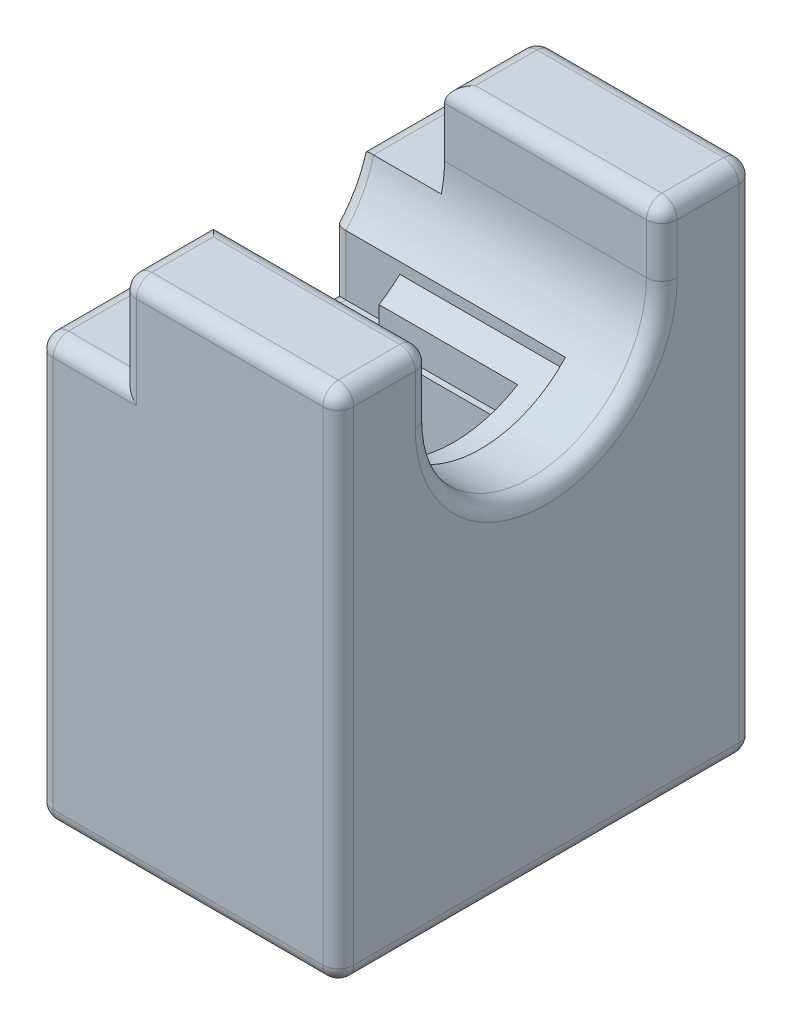
SolidWorks part; units mm, degrees
ref_plane "Front Plane" through (0, 0, 0) normal (0, 0, 1) x (1, 0, 0)
ref_plane "Top Plane" through (0, 0, 0) normal (0, 1, 0) x (1, 0, 0)
ref_plane "Right Plane" through (0, 0, 0) normal (1, 0, 0) x (0, 0, -1)
sketch "Croquis18" plane through (0, 0, 0) normal (0, 1, 0) x (1, 0, 0)
  line L0 (58.8531, -17.2077) -> (58.8531, 10.7923) construction
  line L1 (68.8531, -30.2077) -> (29.8531, -30.2077)
  line L2 (68.8531, -30.2077) -> (68.8531, 23.7923)
  line L3 (68.8531, 23.7923) -> (29.8531, 23.7923)
  line L4 (29.8531, -30.2077) -> (29.8531, 23.7923)
  line L5 (68.8531, -30.2077) -> (29.8531, 23.7923) construction
  line L6 (68.8531, 23.7923) -> (29.8531, -30.2077) construction
  line L7 (40.6531, 17.7923) -> (39.8531, 17.7923) construction
  line L8 (39.8531, 17.7923) -> (39.8531, 14.2923) construction
  line L11 (39.8531, -24.2077) -> (40.6531, -24.2077) construction
  point P0 (0, 0)
  dimension "D1" = 10
  dimension "D2" = 6
  dimension "D3" = 10
  dimension "D4" = 6
extrude "Saliente-Extruir8" add sketch "Croquis18" along normal offset from surface (40.2807 mm away) 1
sketch "Croquis19" plane through (0, 40.2807, 0) normal (0, 1, 0) x (1, 0, 0)
  line L4 (29.8531, -30.2077) -> (68.8531, -30.2077)
  line L5 (68.8531, -30.2077) -> (68.8531, 23.7923)
  line L6 (68.8531, 23.7923) -> (29.8531, 23.7923)
  line L7 (29.8531, 23.7923) -> (29.8531, -30.2077)
  line L8 (29.8531, -30.2077) -> (68.8531, -30.2077)
  line L9 (68.8531, -30.2077) -> (68.8531, 23.7923)
  line L10 (68.8531, 23.7923) -> (29.8531, 23.7923)
  line L11 (29.8531, 23.7923) -> (29.8531, -30.2077)
  dimension "D1" = 0
sketch "Croquis20" plane through (0, 40.2807, 0) normal (0, 1, 0) x (1, 0, 0)
  line L1 (31.4531, -14.2077) -> (60.3531, -14.2077)
  line L2 (60.3531, -14.2077) -> (60.3531, 7.7923)
  line L3 (60.3531, 7.7923) -> (31.4531, 7.7923)
  line L4 (29.8531, -30.2077) -> (68.8531, -30.2077)
  line L5 (68.8531, -30.2077) -> (68.8531, 23.7923)
  line L6 (68.8531, 23.7923) -> (29.8531, 23.7923)
  line L7 (29.8531, 23.7923) -> (29.8531, -30.2077)
  line L8 (29.8531, -30.2077) -> (68.8531, -30.2077)
  line L9 (68.8531, -30.2077) -> (68.8531, 23.7923)
  line L10 (68.8531, 23.7923) -> (29.8531, 23.7923)
  line L11 (29.8531, 23.7923) -> (29.8531, -30.2077)
  line L12 (44.4531, 6.7923) -> (57.4531, 6.7923) construction
  line L13 (44.4531, -13.2077) -> (57.4531, -13.2077) construction
  line L14 (58.8531, -17.2077) -> (58.8531, 10.7923) construction
  line L16 (31.4531, 5.0923) -> (56.8531, 5.0923)
  line L17 (56.8531, 5.0923) -> (56.8531, -11.5077)
  line L18 (56.8531, -11.5077) -> (19.4531, -11.5077)
  line L19 (55.8531, 4.0923) -> (44.4531, 4.0923) construction
  line L20 (44.4531, -10.5077) -> (55.8531, -10.5077) construction
  line L21 (55.8531, -10.5077) -> (55.8531, 4.0923) construction
  line L22 (31.4531, 7.7923) -> (38.8531, 7.7923)
  line L23 (38.8531, 7.7923) -> (38.8531, -14.2077)
  line L24 (38.8531, -14.2077) -> (31.4531, -14.2077)
  line L25 (19.4531, -11.5077) -> (38.8531, -11.5077)
  line L26 (31.4531, 5.0923) -> (38.8531, 5.0923)
  line L27 (39.8531, 10.3477) -> (39.8531, -16.7632) construction
  point P22 (38.1531, -11.5077)
  dimension "D2" = 1
  dimension "D3" = 1
  dimension "D4" = 1.5
  dimension "D5" = 1
  dimension "D6" = 1
  dimension "D7" = 1
  dimension "D8" = 1
  dimension "D1" = 0
extrude "Saliente-Extruir9" add sketch "Croquis20" along normal offset from surface (6.381 mm away) 1
sketch "Croquis21" plane through (0, 40.2807, 0) normal (0, 1, 0) x (1, 0, 0)
  line L9 (29.8531, 23.7923) -> (68.8531, 23.7923)
  line L10 (29.8531, 23.7923) -> (29.8531, -30.2077)
  line L11 (29.8531, -30.2077) -> (68.8531, -30.2077)
  line L12 (68.8531, 23.7923) -> (68.8531, -30.2077)
  line L13 (26.8531, 7.7923) -> (60.3531, 7.7923)
  line L14 (26.8531, 7.7923) -> (26.8531, -14.2077)
  line L15 (26.8531, -14.2077) -> (60.3531, -14.2077)
  line L16 (60.3531, 7.7923) -> (60.3531, -14.2077)
  dimension "D1" = 42
  dimension "D2" = 22
extrude "Saliente-Extruir10" add sketch "Croquis21" along normal offset from surface (26.5 mm away) 5
sketch "Croquis22" plane through (68.8531, 0, 0) normal (1, 0, 0) x (0, 0, -1)
  circle A0 centre (-3.2077, 58.2807) radius 15
  dimension "D1" = 30
extrude "Cortar-Extruir8" cut sketch "Croquis22" against normal up to surface (39 mm away)
sketch "Croquis23" plane through (68.8531, 0, 0) normal (1, 0, 0) x (0, 0, -1)
  line L0 (-18.2077, 73.6247) -> (-18.2077, 44.0051)
  line L1 (11.7923, 73.6247) -> (11.7923, 42.9491)
  line L2 (20.5232, 66.7807) -> (-27.1005, 66.7807)
  line L3 (9.1515, 66.7807) -> (23.7923, 66.7807) construction
  line L4 (-30.2077, 66.7807) -> (-15.5669, 66.7807) construction
  arc A0 (-15.5669, 66.7807) -> (9.1515, 66.7807) centre (-3.2077, 58.2807) ccw construction
  arc A1 (-15.5669, 66.7807) -> (9.1515, 66.7807) centre (-3.2077, 58.2807) ccw
  line M3 (23.7923, 66.7807) -> (9.1515, 66.7807)
  arc M4 (9.1515, 66.7807) -> (-15.5669, 66.7807) centre (-3.2077, 58.2807) cw
  line M5 (-15.5669, 66.7807) -> (-30.2077, 66.7807)
extrude "Cortar-Extruir9" cut sketch "Croquis23" against normal through all contours L0 M5 M4 | L1 M3 M4
sketch "Croquis24" plane through (0, 66.7807, 0) normal (0, 1, 0) x (1, 0, 0)
  line L0 (40.6531, 10.3477) -> (40.6531, 14.2923) construction
  line L1 (29.8531, -30.2077) -> (40.6531, -30.2077)
  line L2 (29.8531, -30.2077) -> (29.8531, 23.7923)
  line L3 (29.8531, 23.7923) -> (40.6531, 23.7923)
  line L4 (40.6531, -30.2077) -> (40.6531, 23.7923)
  line L5 (68.8531, 23.7923) -> (29.8531, 23.7923) construction
extrude "Cortar-Extruir10" cut sketch "Croquis24" against normal up to vertex (12 mm away)
sketch "Croquis25" plane through (40.6531, 0, 0) normal (-1, 0, 0) x (0, 0, 1)
  circle A0 centre (20.7077, 58.2807) radius 2.25
  circle A1 centre (-14.2923, 58.2807) radius 2.25
  dimension "D1" = 4.5
  dimension "D2" = 4.5
extrude "Cortar-Extruir11" cut sketch "Croquis25" against normal offset from surface (24.2 mm away) 4 up to face at (68.8531, 46.0855, 3.2077)
fillet "Redondeo1" radius 2 26 edges at (29.8531, 0, 3.2077) (29.8531, 54.7807, -17.5852) (29.8531, 51.2008, -10.0163) (29.8531, 51.2008, 16.4318) (29.8531, 54.7807, 24.0007) (29.8531, 27.3903, -23.7923) (49.3531, 0, -23.7923) (54.7531, 66.7807, -23.7923) (40.6531, 60.7807, -23.7923) (35.2531, 54.7807, -23.7923) (68.8531, 62.5307, -11.7923) (68.8531, 66.7807, -17.7923) (68.8531, 33.3903, -23.7923) (68.8531, 0, 3.2077) (68.8531, 66.7807, 24.2077) (68.8531, 62.5307, 18.2077) (68.8531, 43.2807, 3.2077) (68.8531, 33.3903, 30.2077) (49.3531, 0, 30.2077) (29.8531, 27.3903, 30.2077) (35.2531, 54.7807, 30.2077) (40.6531, 60.7807, 30.2077) (54.7531, 66.7807, 30.2077) (29.8531, 44.1816, -7.7923) (29.8531, 40.2807, 3.2077) (29.8531, 44.1816, 14.2077)
fillet "Redondeo2" radius 2 8 edges at (41.2389, 66.1949, 29.622) (41.2389, 66.1949, -23.2065) (68.2673, 66.1949, -12.378) (68.2673, 66.1949, 18.7935) (40.6531, 66.7807, 23.2077) (40.6531, 66.7807, -16.7923) (53.7531, 66.7807, -11.7923) (53.7531, 66.7807, 18.2077)
sketch "Croquis26" plane through (0, 0, 0) normal (0, -1, 0) x (1, 0, 0)
  line L0 (31.8531, 30.2077) -> (66.8531, 30.2077) construction
  line L1 (29.8531, -21.7923) -> (29.8531, 28.2077) construction
  line L2 (68.8531, 28.2077) -> (68.8531, -21.7923) construction
  line L3 (66.8531, -23.7923) -> (31.8531, -23.7923) construction
  circle A0 centre (39.8531, 20.2077) radius 2.25
  circle A1 centre (58.8531, 20.2077) radius 2.25
  circle A2 centre (39.8531, -13.7923) radius 2.25
  circle A3 centre (58.8531, -13.7923) radius 2.25
  dimension "D1" = 4.5
  dimension "D2" = 10
  dimension "D3" = 10
  dimension "D4" = 10
  dimension "D5" = 10
  dimension "D6" = 10
  dimension "D7" = 10
  dimension "D8" = 10
  dimension "D9" = 10
extrude "Cortar-Extruir12" cut sketch "Croquis26" against normal blind 30
sketch "Croquis27" plane through (0, 0, 0) normal (0, -1, 0) x (1, 0, 0)
  line L1 (41.8531, 10.7077) -> (56.8531, 10.7077)
  line L2 (41.8531, 10.7077) -> (41.8531, -4.2923)
  line L3 (41.8531, -4.2923) -> (56.8531, -4.2923)
  line L4 (56.8531, 10.7077) -> (56.8531, -4.2923)
  line L5 (34.9423, 30.2077) -> (34.9423, 3.2077) construction
  line L7 (31.8531, 30.2077) -> (66.8531, 30.2077) construction
  line L9 (34.9423, 3.2077) -> (34.9423, -23.7923) construction
  line L11 (66.8531, -23.7923) -> (31.8531, -23.7923) construction
  line L14 (29.8531, 25.749) -> (49.3531, 25.749) construction
  line L15 (29.8531, -21.7923) -> (29.8531, 28.2077) construction
  line L16 (49.3531, 25.749) -> (68.8531, 25.749) construction
  line L17 (68.8531, 28.2077) -> (68.8531, -21.7923) construction
  point P4 (41.8531, 3.2077)
  point P6 (49.3531, 10.7077)
  dimension "D1" = 15
  dimension "D2" = 15
extrude "Cortar-Extruir13" cut sketch "Croquis27" against normal through all
